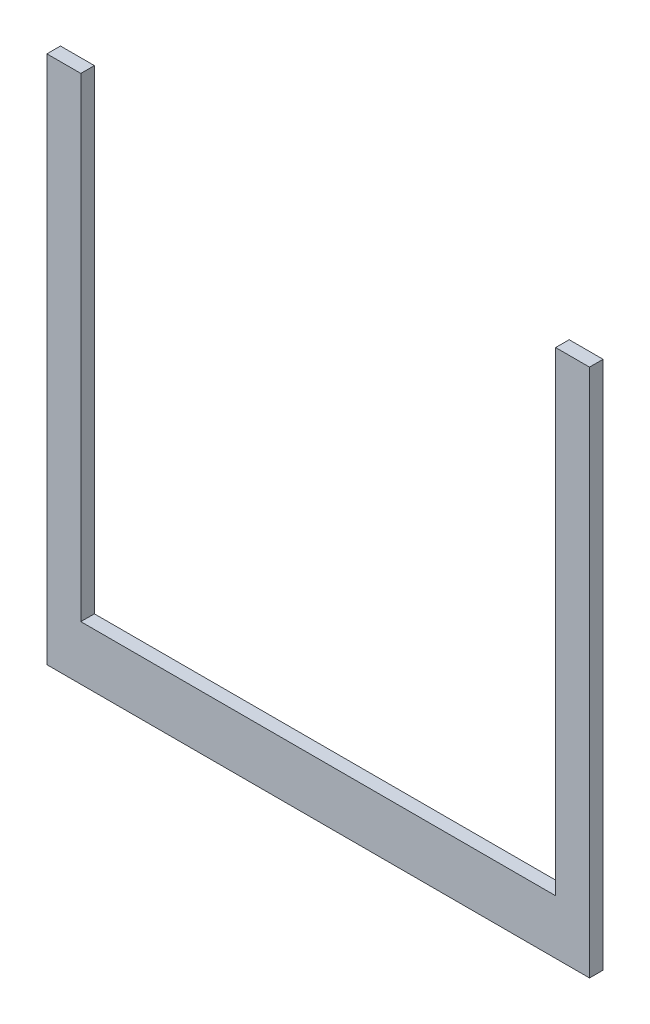
SolidWorks part; units mm, degrees
ref_plane "Front Plane" through (0, 0, 0) normal (0, 0, 1) x (1, 0, 0)
ref_plane "Top Plane" through (0, 0, 0) normal (0, 1, 0) x (1, 0, 0)
ref_plane "Right Plane" through (0, 0, 0) normal (1, 0, 0) x (0, 0, -1)
sketch "Sketch1" plane through (0, 0, 0) normal (0, 0, 1) x (1, 0, 0)
  line L0 (0, 390) -> (25, 390)
  line L1 (25, 390) -> (25, 40)
  line L2 (25, 40) -> (375, 40)
  line L3 (375, 40) -> (375, 390)
  line L4 (375, 390) -> (400, 390)
  line L5 (400, 390) -> (400, 0)
  line L6 (400, 0) -> (0, 0)
  line L7 (0, 0) -> (0, 390)
  point P7 (0, 0)
  point P9 (0, 0)
  point P10 (0, 0)
  point P12 (0, 0)
  point P13 (0, 0)
  dimension "D1" = 25
  dimension "D2" = 400
  dimension "D3" = 350
  dimension "D4" = 390
extrude "Boss-Extrude1" add sketch "Sketch1" along normal blind 10
